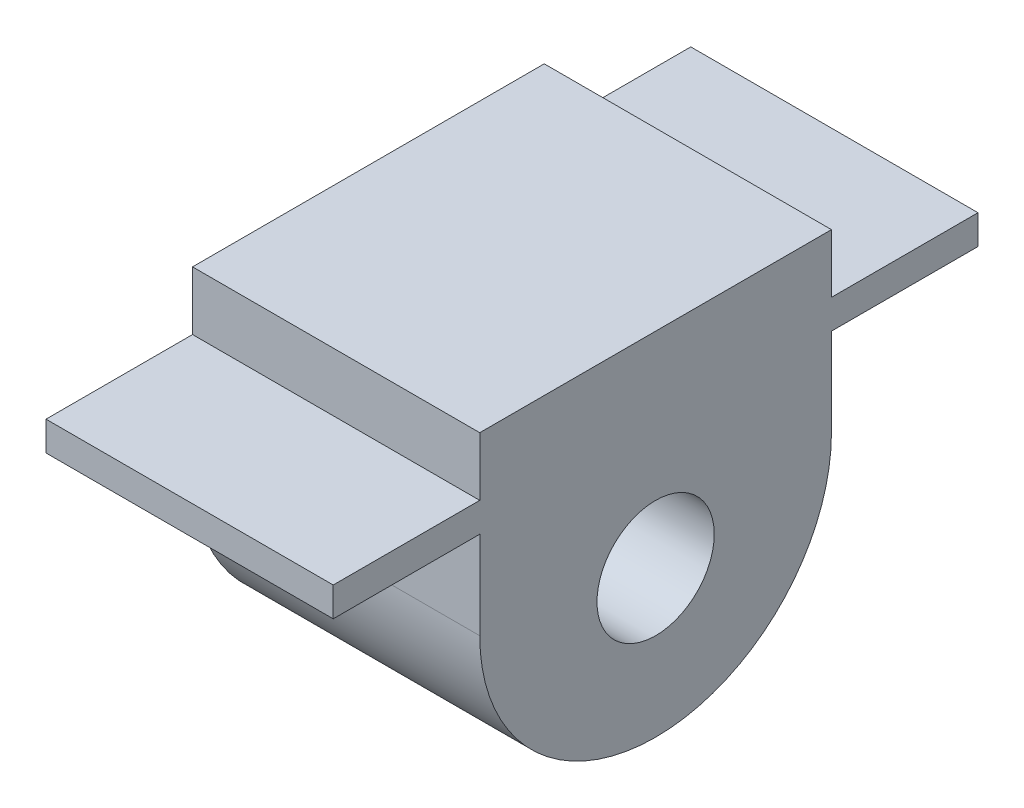
SolidWorks part; units mm, degrees
ref_plane "Front Plane" through (0, 0, 0) normal (0, 0, 1) x (1, 0, 0)
ref_plane "Top Plane" through (0, 0, 0) normal (0, 1, 0) x (1, 0, 0)
ref_plane "Right Plane" through (0, 0, 0) normal (1, 0, 0) x (0, 0, -1)
sketch "Sketch1" plane through (0, 0, 0) normal (0, 1, 0) x (1, 0, 0)
  line L0 (-49.5, -12.5) -> (-49.5, 12.5)
  line L1 (-46.5, -9.5) -> (46.5, -9.5)
  line L2 (-46.5, -9.5) -> (-46.5, 9.5)
  line L3 (-46.5, 9.5) -> (46.5, 9.5)
  line L4 (46.5, -9.5) -> (46.5, 9.5)
  line L5 (-46.5, -9.5) -> (46.5, 9.5) construction
  line L6 (-46.5, 9.5) -> (46.5, -9.5) construction
  line L7 (-49.5, 12.5) -> (49.5, 12.5)
  line L8 (49.5, -12.5) -> (49.5, 12.5)
  line L9 (-49.5, -12.5) -> (49.5, -12.5)
  point P0 (0, 0)
  dimension "D1" = 19
  dimension "D2" = 93
  dimension "D3" = 3
extrude "Boss-Extrude1" add sketch "Sketch1" along normal blind 10
sketch "Sketch2" plane through (0, 0, 12.5) normal (0, 0, 1) x (1, 0, 0)
  circle A0 centre (21.7809, 42.8531) radius 40
  dimension "D1" = 80
extrude "Cut-Extrude1" cut sketch "Sketch2" against normal blind 8
sketch "Sketch5" plane through (0, 0, 0) normal (0, -1, 0) x (1, 0, 0)
  line L7 (49.5, -12.5) -> (-49.5, -12.5) construction
  line L8 (-24.5, -12.5) -> (-34.5, -12.5)
  line L9 (-24.5, -12.5) -> (-24.5, 12.5)
  line L10 (-24.5, 12.5) -> (-34.5, 12.5)
  line L11 (-34.5, -12.5) -> (-34.5, 12.5)
  line L12 (-49.5, 12.5) -> (49.5, 12.5) construction
  line L13 (-49.5, -12.5) -> (-49.5, 12.5) construction
  dimension "D1" = 10
  dimension "D2" = 15
extrude "Boss-Extrude5" add sketch "Sketch5" against normal blind 2
sketch "Sketch6" plane through (0, 0, 0) normal (0, -1, 0) x (1, 0, 0)
  line L0 (46.5, -9.5) -> (-24.5, -9.5) construction
  line L1 (46.5, 9.5) -> (40.5, 9.5)
  line L2 (46.5, 9.5) -> (46.5, -9.5)
  line L3 (46.5, -9.5) -> (40.5, -9.5)
  line L4 (40.5, 9.5) -> (40.5, -9.5)
  dimension "D1" = 6
extrude "Boss-Extrude6" add sketch "Sketch6" against normal blind 2
sketch "Sketch7" plane through (0, 10, 0) normal (0, 1, 0) x (1, 0, 0)
  line L0 (-49.5, -12.5) -> (-1.0373, -12.5) construction
  line L1 (-36.5, -12.5) -> (-28.5, -12.5)
  line L2 (-36.5, -12.5) -> (-36.5, -9.5)
  line L3 (-36.5, -9.5) -> (-28.5, -9.5)
  line L4 (-28.5, -12.5) -> (-28.5, -9.5)
  line L5 (-46.5, -9.5) -> (-1.0373, -9.5) construction
  line L6 (-49.5, 12.5) -> (-49.5, -12.5) construction
  dimension "D1" = 8
  dimension "D2" = 13
extrude "Boss-Extrude7" add sketch "Sketch7" along normal blind 30
fillet "Fillet5" radius 3 6 edges at (-34.5, 1, 9.5) (-34.5, 1, -9.5) (-24.5, 1, 9.5) (-24.5, 1, -9.5) (40.5, 1, 9.5) (40.5, 1, -9.5)
fillet "Fillet7" radius 5 1 edges at (44.5992, 10, 11)
fillet "Fillet8" radius 20 1 edges at (-1.0373, 10, 11)
fillet "Fillet9" radius 1.5 8 edges at (-46.5, 5, 9.5) (-46.5, 5, -9.5) (46.5, 6, -9.5) (46.5, 6, 9.5) (49.5, 5, 12.5) (49.5, 5, -12.5) (-49.5, 5, 12.5) (-49.5, 5, -12.5)
fillet "Fillet10" radius 6 2 edges at (-36.5, 10, 11) (-28.5, 10, 11)
fillet "Fillet11" radius 3 2 edges at (-28.5, 40, 11) (-36.5, 40, 11)
sketch "Sketch8" plane through (0, 0, 0) normal (0, -1, 0) x (1, 0, 0)
  line L0 (48, -12.5) -> (-48, -12.5) construction
  line L1 (-10, 12.5) -> (10, 12.5)
  line L2 (-10, 12.5) -> (-10, -12.5)
  line L3 (-10, -12.5) -> (10, -12.5)
  line L4 (10, 12.5) -> (10, -12.5)
  line L5 (-10, 12.5) -> (10, -12.5) construction
  line L6 (-10, -12.5) -> (10, 12.5) construction
  point P0 (0, 0)
  dimension "D1" = 20
extrude "Boss-Extrude8" add sketch "Sketch8" against normal up to surface (2 mm away) up to face at (-29.5, 2, 0)
sketch "Sketch9" plane through (0, 0, 0) normal (0, -1, 0) x (1, 0, 0)
  line L1 (-4.9, 6) -> (4.9, 6)
  line L2 (-4.9, 6) -> (-4.9, -6)
  line L3 (-4.9, -6) -> (4.9, -6)
  line L4 (4.9, 6) -> (4.9, -6)
  line L5 (-4.9, 6) -> (4.9, -6) construction
  line L6 (-4.9, -6) -> (4.9, 6) construction
  point P0 (0, 0)
  dimension "D1" = 9.8
  dimension "D2" = 12
extrude "Boss-Extrude9" add sketch "Sketch9" along normal blind 10
sketch "Sketch10" plane through (4.9, 0, 0) normal (1, 0, 0) x (0, 0, -1)
  circle A0 centre (0, -5) radius 2
  dimension "D1" = 4
  dimension "D2" = 5
extrude "Cut-Extrude2" cut sketch "Sketch10" against normal blind 23
fillet "Fillet12" radius 6 2 edges at (0, -10, 6) (0, -10, -6)
sketch "Sketch11" plane through (0, 0, 0) normal (0, -1, 0) x (1, 0, 0)
  line L0 (-4.9, 6) -> (4.9, 6)
  line L1 (4.9, 6) -> (4.9, -6)
  line L2 (4.9, -6) -> (-4.9, -6)
  line L3 (-4.9, -6) -> (-4.9, 6)
extrude "Cut-Extrude-Thin1" cut sketch "Sketch11" against normal through all both and the other way through all thin thin type one direction wall 50
sketch "Sketch12" plane through (0, 0, -6) normal (0, 0, -1) x (-1, 0, 0)
  line L0 (0, -10) -> (0, 0) construction
  line L1 (4.9, -10) -> (-4.9, -10) construction
  line L2 (-4.9, 0) -> (4.9, 0)
  line L3 (-4.9, -4) -> (-4.9, 2) construction
  line L4 (4.9, -4) -> (4.9, 2) construction
  line L5 (4.9, 0) -> (4.9, -1)
  line L6 (4.9, -1) -> (-4.9, -1)
  line L7 (-4.9, -1) -> (-4.9, 0)
  dimension "D1" = 10
  dimension "D2" = 1
extrude "Boss-Extrude10" add sketch "Sketch12" along normal blind 5
mirror "Mirror1" about plane through (0, 0, 0) normal (0, 0, 1) of "Boss-Extrude10"
